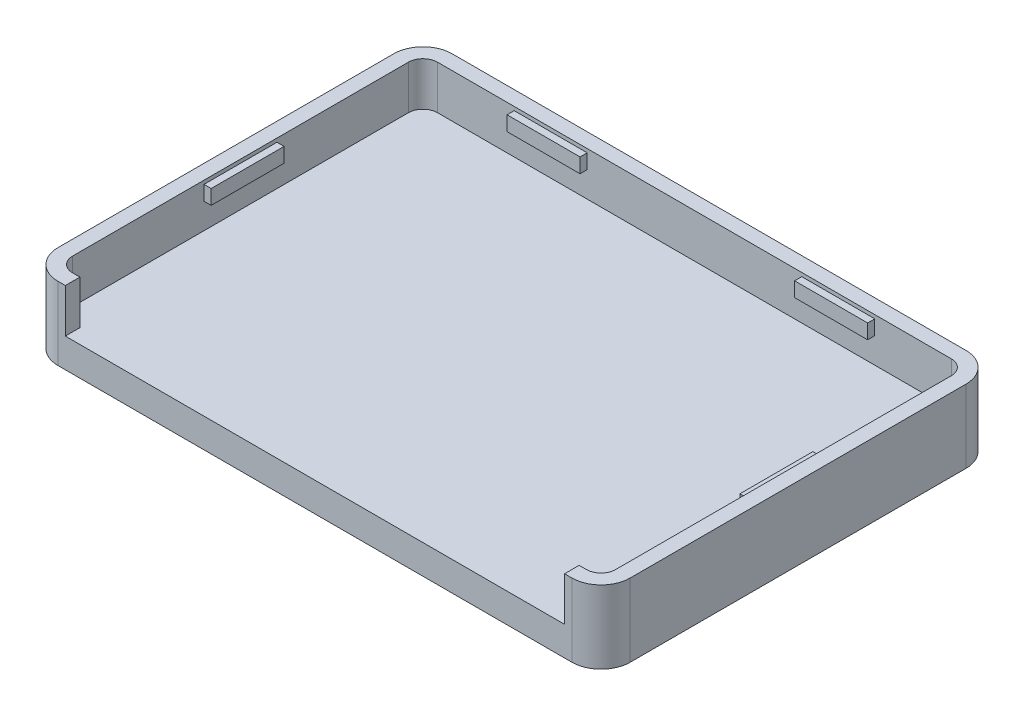
SolidWorks part; units mm, degrees
ref_plane "Plan de face" through (0, 0, 0) normal (0, 0, 1) x (1, 0, 0)
ref_plane "Plan de dessus" through (0, 0, 0) normal (0, 1, 0) x (1, 0, 0)
ref_plane "Plan de droite" through (0, 0, 0) normal (1, 0, 0) x (0, 0, -1)
sketch "Esquisse1" plane through (0, 0, 0) normal (0, 1, 0) x (1, 0, 0)
  line L1 (2, 0) -> (37.2, 0)
  line L2 (0, 2) -> (0, 25)
  line L3 (2, 27) -> (37.2, 27)
  line L4 (39.2, 2) -> (39.2, 25)
  arc A0 (37.2, 0) -> (39.2, 2) centre (37.2, 2) ccw
  arc A1 (37.2, 27) -> (39.2, 25) centre (37.2, 25) cw
  arc A2 (2, 0) -> (0, 2) centre (2, 2) cw
  arc A3 (0, 25) -> (2, 27) centre (2, 25) cw
  point P7 (39.2, 0)
  point P10 (39.2, 27)
  point P13 (0, 0)
  dimension "D3" = 2
  dimension "D1" = 39.2
  dimension "D2" = 27
extrude "Boss.-Extru.1" add sketch "Esquisse1" along normal blind 5
sketch "Esquisse2" plane through (0, 5, 0) normal (0, 1, 0) x (1, 0, 0)
  line L8 (38.2, 2) -> (38.2, 25)
  line L9 (37.2, 26) -> (2, 26)
  line L10 (1, 25) -> (1, 2)
  line L11 (2, 1) -> (37.2, 1)
  line L12 (38.2, 2) -> (38.2, 25)
  line L13 (37.2, 26) -> (2, 26)
  line L14 (1, 25) -> (1, 2)
  line L15 (2, 1) -> (37.2, 1)
  arc A8 (37.2, 1) -> (38.2, 2) centre (37.2, 2) ccw
  arc A9 (38.2, 25) -> (37.2, 26) centre (37.2, 25) ccw
  arc A10 (2, 26) -> (1, 25) centre (2, 25) ccw
  arc A11 (1, 2) -> (2, 1) centre (2, 2) ccw
  arc A12 (37.2, 1) -> (38.2, 2) centre (37.2, 2) ccw
  arc A13 (38.2, 25) -> (37.2, 26) centre (37.2, 25) ccw
  arc A14 (2, 26) -> (1, 25) centre (2, 25) ccw
  arc A15 (1, 2) -> (2, 1) centre (2, 2) ccw
  dimension "D1" = 1
extrude "Enlèv. mat.-Extru.1" cut sketch "Esquisse2" against normal blind 3
sketch "Esquisse3" plane through (0, 0, 0) normal (0, 0, 1) x (1, 0, 0)
  line L0 (2, 5) -> (37.2, 5) construction
  line L1 (2.5, 5) -> (36.7, 5)
  line L2 (2.5, 5) -> (2.5, 2)
  line L3 (2.5, 2) -> (36.7, 2)
  line L4 (36.7, 5) -> (36.7, 2)
  line L5 (2, 5) -> (2, 0) construction
  line L6 (37.2, 5) -> (37.2, 0) construction
  dimension "D1" = 3
  dimension "D2" = 0.5
  dimension "D3" = 0.5
extrude "Enlèv. mat.-Extru.2" cut sketch "Esquisse3" against normal blind 3
sketch "Esquisse4" plane through (1, 0, 0) normal (1, 0, 0) x (0, 0, -1)
  line L0 (25, 5) -> (2, 5) construction
  line L1 (11, 3.75) -> (16, 3.75)
  line L2 (11, 3.75) -> (11, 4.75)
  line L3 (11, 4.75) -> (16, 4.75)
  line L4 (16, 3.75) -> (16, 4.75)
  line L5 (2, 2) -> (2, 5) construction
  point P6 (13.5, 3.75)
  dimension "D1" = 1
  dimension "D2" = 5
  dimension "D3" = 0.25
  dimension "D4" = 11.5
extrude "Boss.-Extru.2" add sketch "Esquisse4" along normal blind 0.489
sketch "Esquisse5" plane through (38.2, 0, 0) normal (-1, 0, 0) x (0, 0, 1)
  line L0 (-2, 5) -> (-25, 5) construction
  line L1 (-16, 4.75) -> (-11, 4.75)
  line L2 (-16, 4.75) -> (-16, 3.75)
  line L3 (-16, 3.75) -> (-11, 3.75)
  line L4 (-11, 4.75) -> (-11, 3.75)
  line L5 (-25, 2) -> (-25, 5) construction
  point P6 (-13.5, 3.75)
  dimension "D1" = 5
  dimension "D2" = 1
  dimension "D3" = 0.25
  dimension "D4" = 11.5
extrude "Boss.-Extru.3" add sketch "Esquisse5" along normal blind 0.489
sketch "Esquisse6" plane through (0, 0, -26) normal (0, 0, 1) x (1, 0, 0)
  line L0 (37.2, 5) -> (2, 5) construction
  line L1 (7.25, 3.75) -> (12.25, 3.75)
  line L2 (7.25, 3.75) -> (7.25, 4.75)
  line L3 (7.25, 4.75) -> (12.25, 4.75)
  line L4 (12.25, 3.75) -> (12.25, 4.75)
  line L5 (2, 2) -> (2, 5) construction
  line L6 (37.2, 2) -> (37.2, 5) construction
  line L7 (31.95, 3.75) -> (26.95, 3.75)
  line L8 (31.95, 3.75) -> (31.95, 4.75)
  line L9 (31.95, 4.75) -> (26.95, 4.75)
  line L10 (26.95, 3.75) -> (26.95, 4.75)
  point P6 (9.75, 3.75)
  point P13 (29.45, 3.75)
  dimension "D1" = 1
  dimension "D2" = 5
  dimension "D3" = 0.25
  dimension "D4" = 7.75
  dimension "D5" = 5
  dimension "D6" = 1
  dimension "D7" = 0.25
  dimension "D8" = 7.75
extrude "Boss.-Extru.4" add sketch "Esquisse6" along normal blind 0.489
